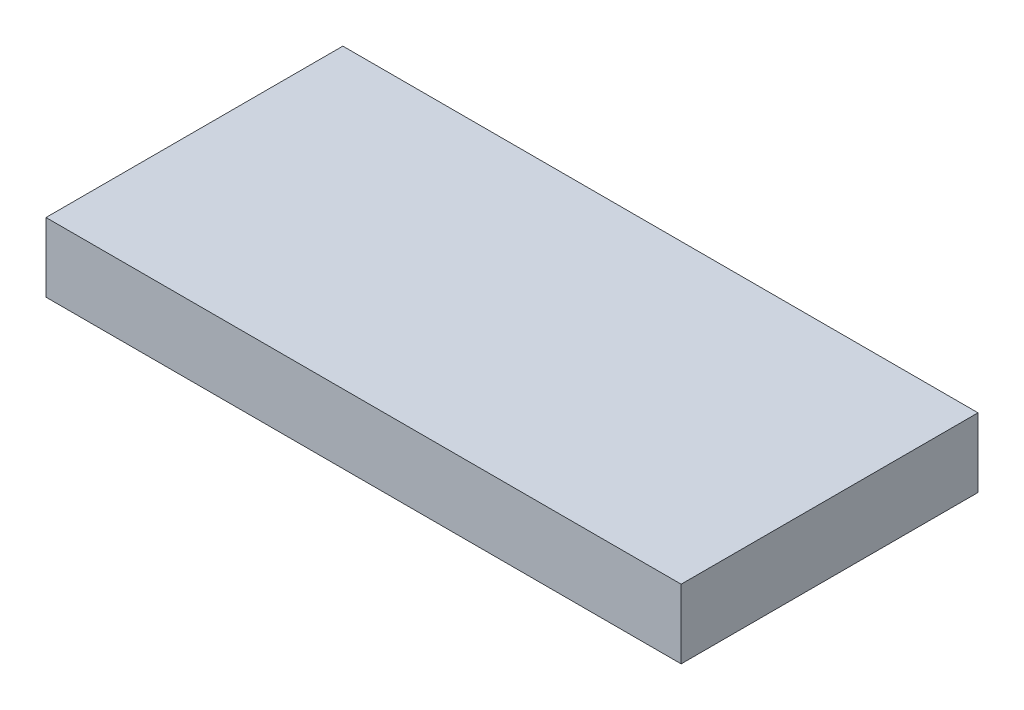
SolidWorks part; units mm, degrees
ref_plane "Front Plane" through (0, 0, 0) normal (0, 0, 1) x (1, 0, 0)
ref_plane "Top Plane" through (0, 0, 0) normal (0, 1, 0) x (1, 0, 0)
ref_plane "Right Plane" through (0, 0, 0) normal (1, 0, 0) x (0, 0, -1)
sketch "Sketch1" plane through (0, 0, 0) normal (0, 1, 0) x (1, 0, 0)
  line L1 (92, 43) -> (-92, 43)
  line L2 (92, 43) -> (92, -43)
  line L3 (92, -43) -> (-92, -43)
  line L4 (-92, 43) -> (-92, -43)
  line L5 (92, 43) -> (-92, -43) construction
  line L6 (92, -43) -> (-92, 43) construction
  point P0 (0, 0)
  dimension "D1" = 184
  dimension "D2" = 86
extrude "Boss-Extrude1" add sketch "Sketch1" along normal blind 20 contours L1 L4 L3 L2
equation "\"D2@Sketch1\"=46+40"
equation "\"D1@Sketch1\"=144+40"
